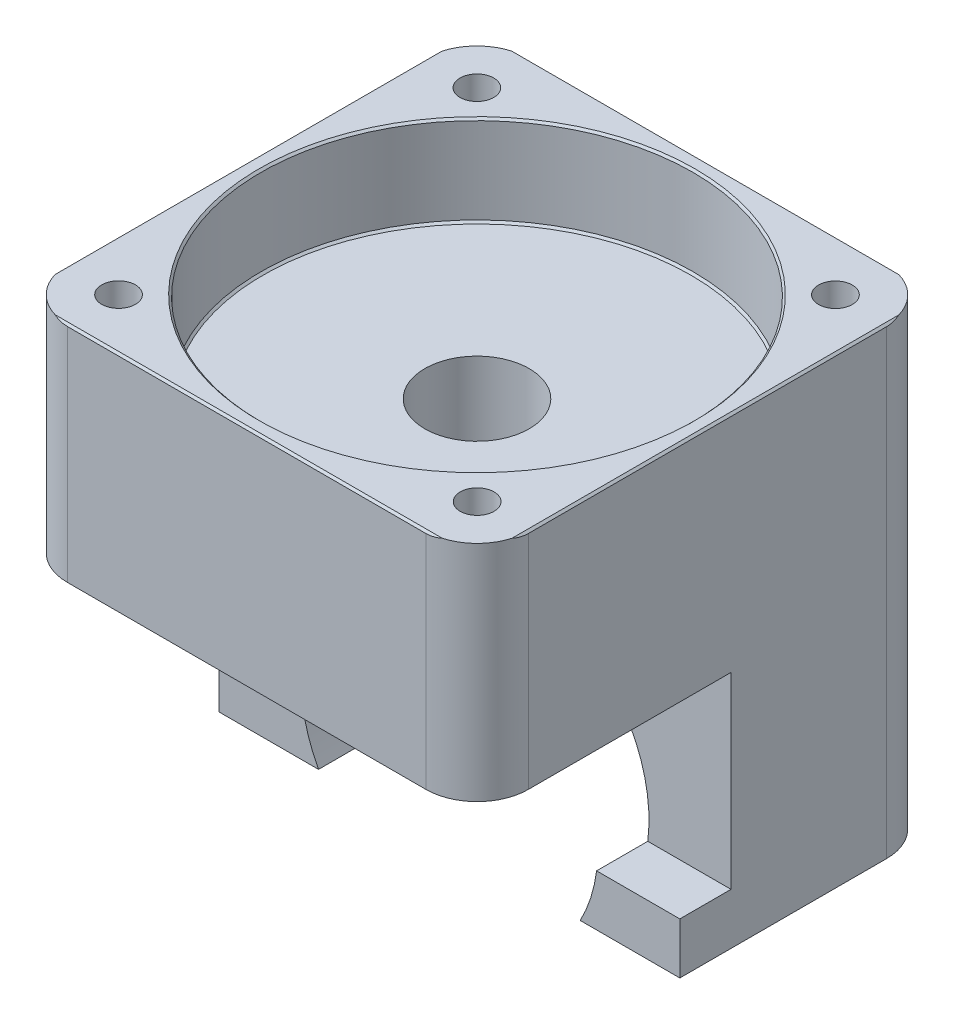
SolidWorks part; units mm, degrees
ref_plane "Front Plane" through (0, 0, 0) normal (0, 0, 1) x (1, 0, 0)
ref_plane "Top Plane" through (0, 0, 0) normal (0, 1, 0) x (1, 0, 0)
ref_plane "Right Plane" through (0, 0, 0) normal (1, 0, 0) x (0, 0, -1)
sketch "Sketch1" plane through (0, 0, 0) normal (0, 1, 0) x (1, 0, 0)
  line L1 (-22.5127, -22.5) -> (22.5127, -22.5)
  line L2 (-22.5127, -22.5) -> (-22.5127, 22.5)
  line L3 (-22.5127, 22.5) -> (22.5127, 22.5)
  line L4 (22.5127, -22.5) -> (22.5127, 22.5)
  line L5 (-22.5127, -22.5) -> (22.5127, 22.5) construction
  line L6 (-22.5127, 22.5) -> (22.5127, -22.5) construction
  circle A0 centre (0, 0) radius 21.05 construction
  circle A1 centre (0, 0) radius 22.5 construction
  point P8 (0, 22.5)
  dimension "D1" = 42.1
  dimension "D2" = 45
extrude "Boss-Extrude1" add sketch "Sketch1" along normal blind 60
sketch "Sketch2" plane through (0, 60, 0) normal (0, 1, 0) x (1, 0, 0)
  circle A0 centre (0, 0) radius 21.1
  dimension "D1" = 42.2
extrude "Cut-Extrude1" cut sketch "Sketch2" against normal blind 8.8
sketch "Sketch3" plane through (0, 51.2, 0) normal (0, 1, 0) x (1, 0, 0)
  circle A0 centre (0, 0) radius 5.1
  dimension "D1" = 10.2
extrude "Cut-Extrude2" cut sketch "Sketch3" against normal blind 11.8
chamfer "Chamfer1" distance 0.2 angle 45 6 edges at (0, 60, 21.1) (0, 51.2, 21.1) (0, 60, 22.5) (-22.5127, 60, 0) (0, 60, -22.5) (22.5127, 60, 0)
sketch "Sketch4" plane through (0, 0, 22.5) normal (0, 0, 1) x (1, 0, 0)
  line L0 (0, 0) -> (0, 5) construction
  circle A0 centre (0, 21.6507) radius 14.5
  dimension "D2" = 29
  dimension "D1" = 5
extrude "Cut-Extrude3" cut sketch "Sketch4" against normal through all
sketch "Sketch5" plane through (0, 0, 0) normal (0, -1, 0) x (1, 0, 0)
  line L1 (-22.5127, -22.5) -> (22.5127, -22.5)
  line L2 (-22.5127, -22.5) -> (-22.5127, 22.5)
  line L3 (-22.5127, 22.5) -> (22.5127, 22.5)
  line L4 (22.5127, -22.5) -> (22.5127, 22.5)
  line L5 (-22.5127, -22.5) -> (22.5127, 22.5) construction
  line L6 (-22.5127, 22.5) -> (22.5127, -22.5) construction
  point P0 (0, 0)
extrude "Cut-Extrude4" cut sketch "Sketch5" against normal blind 14.8
sketch "Sketch6" plane through (0, 0, 22.5) normal (0, 0, 1) x (1, 0, 0)
  line L0 (-22.5127, 59.8) -> (-22.5127, 14.8) construction
  line L1 (-22.5127, 38.1507) -> (22.5127, 38.1507)
  line L2 (-22.5127, 38.1507) -> (-22.5127, 14.8)
  line L3 (-22.5127, 14.8) -> (22.5127, 14.8)
  line L4 (22.5127, 38.1507) -> (22.5127, 14.8)
extrude "Cut-Extrude5" cut sketch "Sketch6" against normal blind 24.8
fillet "Fillet3" radius 5 2 edges at (22.5127, 37.3, -22.5) (22.4127, 59.9, -22.4)
fillet "Fillet4" radius 5 2 edges at (-22.5127, 37.3, -22.5) (-22.4127, 59.9, -22.4)
fillet "Fillet7" radius 5 2 edges at (22.5127, 48.9753, 22.5) (22.4127, 59.9, 22.4)
fillet "Fillet8" radius 5 2 edges at (-22.5127, 48.9753, 22.5) (-22.4127, 59.9, 22.4)
sketch "Sketch7" plane through (0, 0, -2.3) normal (0, 0, 1) x (1, 0, 0)
  line L1 (-22.5127, 14.8) -> (-12.7796, 14.8)
  line L2 (-22.5127, 14.8) -> (-22.5127, 19.8)
  line L3 (-22.5127, 19.8) -> (-14.3814, 19.8)
  arc A0 (-12.7796, 14.8) -> (-14.3814, 19.8) centre (0, 21.6507) cw
  dimension "D1" = 5
extrude "Boss-Extrude3" add sketch "Sketch7" along normal blind 5
mirror "Mirror1" about plane through (0, 0, 0) normal (1, 0, 0) of "Boss-Extrude3"
sketch "Sketch8" plane through (0, 0, -2.3) normal (0, 0, 1) x (1, 0, 0)
  line L0 (-22.5127, 38.1507) -> (-22.5127, 14.8)
sketch "Sketch9" plane through (0, 60, 0) normal (0, 1, 0) x (1, 0, 0)
  line L0 (-21.0482, -21.0355) -> (21.0482, 21.0355) construction
  arc A0 (-22.3127, -18.9) -> (-18.9127, -22.3) centre (-17.5127, -17.5) ccw construction
  arc A1 (22.3127, 18.9) -> (18.9127, 22.3) centre (17.5127, 17.5) ccw construction
  circle A2 centre (-17.5127, 17.5) radius 1.65
  dimension "D1" = 3.3
extrude "Cut-Extrude6" cut sketch "Sketch9" against normal blind 5
mirror "Mirror2" about plane through (0, 0, 0) normal (1, 0, 0) of "Cut-Extrude6" second plane through (0, 0, 0) second plane normal (0, 0, 1)
